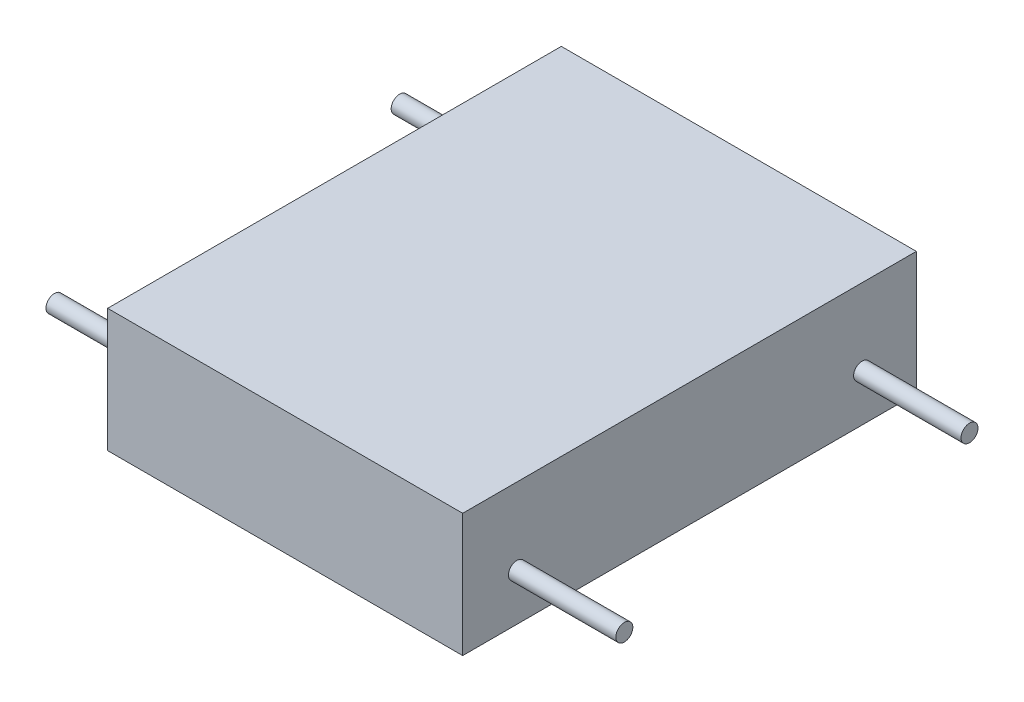
SolidWorks part; units mm, degrees
ref_plane "前视基准面" through (0, 0, 0) normal (0, 0, 1) x (1, 0, 0)
ref_plane "上视基准面" through (0, 0, 0) normal (0, 1, 0) x (1, 0, 0)
ref_plane "右视基准面" through (0, 0, 0) normal (1, 0, 0) x (0, 0, -1)
other "Configuration Table"
sketch "草图1" plane through (0, 0, 0) normal (0, 1, 0) x (1, 0, 0)
  line L1 (-72.1535, 36.9979) -> (71.8465, 36.9979)
  line L2 (-72.1535, 36.9979) -> (-72.1535, -147.0021)
  line L3 (-72.1535, -147.0021) -> (71.8465, -147.0021)
  line L4 (71.8465, 36.9979) -> (71.8465, -147.0021)
  dimension "D1" = 144
  dimension "D2" = 184
extrude "凸台-拉伸1" add sketch "草图1" along normal blind 50
sketch "草图2" plane through (-72.1535, 0, 0) normal (-1, 0, 0) x (0, 0, 1)
  line L0 (-36.9979, 0) -> (147.0021, 0) construction
  line L1 (-36.9979, 50) -> (-36.9979, 0) construction
  circle A0 centre (-14.9979, 19) radius 3.45
  dimension "D3" = 6.9
  dimension "D1" = 19
  dimension "D2" = 22
extrude "凸台-拉伸2" add sketch "草图2" along normal blind 43.56
ref_plane "基准面1" through (-0.1535, 0, 0) normal (-1, 0, 0) x (0, 0, 1)
ref_plane "基准面2" through (0, 0, 55.0021) normal (0, 0, -1) x (-1, 0, 0)
mirror "镜向1" about plane through (-0.1535, 0, 0) normal (-1, 0, 0) of "凸台-拉伸2" second plane through (0, 0, 55.0021) second plane normal (0, 0, -1)
ref_axis "基准轴1" through (115.4065, 19, 125.0021) along (-1, 0, 0)
ref_axis "基准轴2" through (115.4065, 19, -14.9979) along (-1, 0, 0)
ref_axis "基准轴3" through (-115.7135, 19, 125.0021) along (1, 0, 0)
ref_axis "基准轴4" through (-115.7135, 19, -14.9979) along (1, 0, 0)
ref_point "点2"
ref_point "轮点1"
ref_point "轮点2"
ref_point "轮点3"
ref_point "轮点4"
